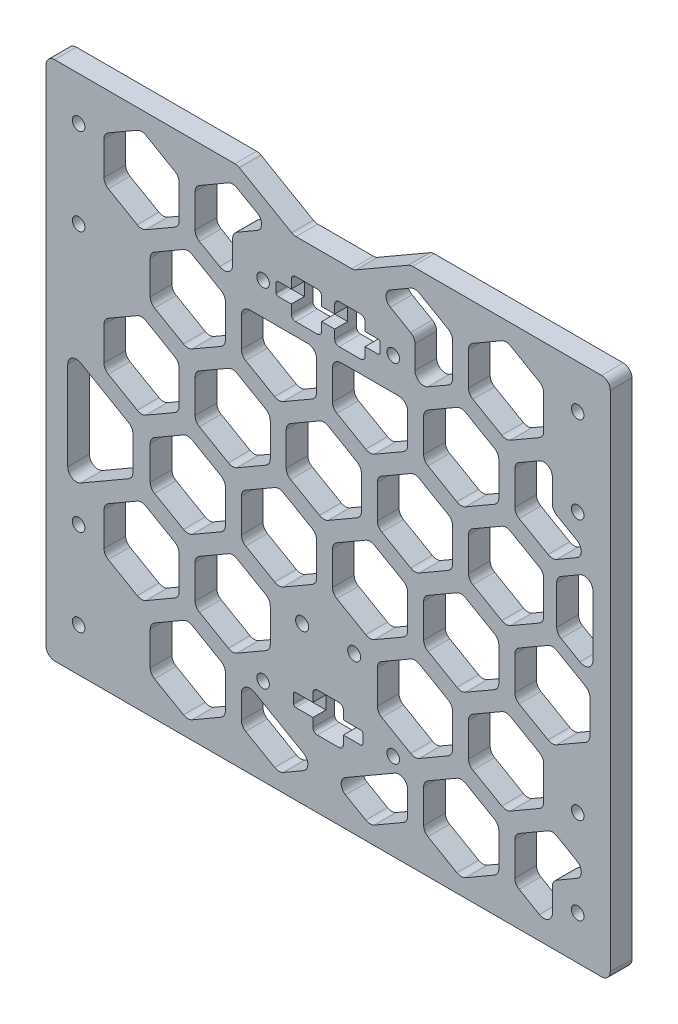
SolidWorks part; units mm, degrees
material "Thornel Mat VMA"
ref_plane "前视基准面" through (0, 0, 0) normal (0, 0, 1) x (1, 0, 0)
ref_plane "上视基准面" through (0, 0, 0) normal (0, 1, 0) x (1, 0, 0)
ref_plane "右视基准面" through (0, 0, 0) normal (1, 0, 0) x (0, 0, -1)
sketch "草图1" plane through (0, 0, 0) normal (0, 0, 1) x (1, 0, 0)
  line L0 (-57.5, -60) -> (-57.5, 60) construction
  line L1 (-65, -60) -> (65, -60)
  line L2 (-65, -60) -> (-65, 60)
  line L3 (-65, 60) -> (65, 60)
  line L4 (65, -60) -> (65, 60)
  line L5 (-65, -60) -> (65, 60) construction
  line L6 (-65, 60) -> (65, -60) construction
  line L7 (0, -1000) -> (0, 49000) construction
  line L8 (57.5, -60) -> (57.5, 60) construction
  line L9 (-57.5, 50) -> (57.5, 30) construction
  line L10 (-57.5, -30) -> (57.5, -50) construction
  line L11 (15, 40) -> (-15, 40) construction
  line L12 (15, -40) -> (-15, -40) construction
  circle A0 centre (-57.5, -50) radius 1.45
  circle A1 centre (-57.5, -30) radius 1.45
  circle A2 centre (-57.5, 30) radius 1.45
  circle A3 centre (-57.5, 50) radius 1.45
  circle A4 centre (57.5, 50) radius 1.45
  circle A5 centre (57.5, 30) radius 1.45
  circle A6 centre (57.5, -30) radius 1.45
  circle A7 centre (57.5, -50) radius 1.45
  circle A8 centre (-15, 40) radius 1.45
  circle A9 centre (15, 40) radius 1.45
  circle A10 centre (-15, -40) radius 1.45
  circle A11 centre (15, -40) radius 1.45
  point P0 (0, 0)
  point P31 (0, 40)
  point P34 (0, -40)
  dimension "D2" = 2.9
  dimension "D9" = 2.9
  dimension "D1" = 130
  dimension "D3" = 20
  dimension "D4" = 60
  dimension "D5" = 20
  dimension "D6" = 10
  dimension "D7" = 10
  dimension "D8" = 7.5
  dimension "D10" = 30
  dimension "D11" = 30
extrude "凸台-拉伸1" add sketch "草图1" along normal blind 5
sketch "草图2" plane through (0, 0, 5) normal (0, 0, 1) x (1, 0, 0)
  line L0 (-57.5, 50) -> (57.5, 30) construction
  line L1 (-8, -41.5) -> (8, -41.5)
  line L2 (-8, -41.5) -> (-8, -38.5)
  line L3 (-8, -38.5) -> (8, -38.5)
  line L4 (8, -41.5) -> (8, -38.5)
  line L5 (-8, -41.5) -> (8, -38.5) construction
  line L6 (-8, -38.5) -> (8, -41.5) construction
  line L7 (-12, 38.5) -> (12, 38.5)
  line L8 (-12, 38.5) -> (-12, 41.5)
  line L9 (-12, 41.5) -> (12, 41.5)
  line L10 (12, 38.5) -> (12, 41.5)
  line L11 (-12, 38.5) -> (12, 41.5) construction
  line L12 (-12, 41.5) -> (12, 38.5) construction
  line L13 (-57.5, -30) -> (57.5, -50) construction
  point P0 (0, -40)
  point P5 (0, 40)
  point P20 (0, 40)
  point P22 (0, -40)
  dimension "D1" = 3
  dimension "D2" = 24
  dimension "D3" = 3
  dimension "D4" = 16
extrude "切除-拉伸1" cut sketch "草图2" against normal blind 3
sketch "草图3" plane through (0, 0, 5) normal (0, 0, 1) x (1, 0, 0)
  line L0 (-57.5, 50) -> (57.5, 30) construction
  line L1 (-57.5, -30) -> (57.5, -50) construction
  line L2 (0, -960) -> (0, 49040) construction
  line L3 (-3.5, -44.5) -> (3.5, -44.5)
  line L4 (-3.5, -44.5) -> (-3.5, -35.5)
  line L5 (-3.5, -35.5) -> (3.5, -35.5)
  line L6 (3.5, -44.5) -> (3.5, -35.5)
  line L7 (-3.5, -44.5) -> (3.5, -35.5) construction
  line L8 (-3.5, -35.5) -> (3.5, -44.5) construction
  line L9 (-8.5, 35.5) -> (-1.5, 35.5)
  line L10 (-8.5, 35.5) -> (-8.5, 44.5)
  line L11 (-8.5, 44.5) -> (-1.5, 44.5)
  line L12 (-1.5, 35.5) -> (-1.5, 44.5)
  line L13 (-8.5, 35.5) -> (-1.5, 44.5) construction
  line L14 (-8.5, 44.5) -> (-1.5, 35.5) construction
  line L15 (8.5, 44.5) -> (1.5, 35.5) construction
  line L16 (8.5, 35.5) -> (1.5, 44.5) construction
  line L17 (1.5, 35.5) -> (1.5, 44.5)
  line L18 (8.5, 44.5) -> (1.5, 44.5)
  line L19 (8.5, 35.5) -> (8.5, 44.5)
  line L20 (8.5, 35.5) -> (1.5, 35.5)
  point P8 (0, -40)
  point P13 (-5, 40)
  point P23 (0, 40)
  point P28 (5, 40)
  dimension "D1" = 5
  dimension "D2" = 7
  dimension "D3" = 9
  dimension "D4" = 7
  dimension "D5" = 9
extrude "切除-拉伸2" cut sketch "草图3" against normal through all
sketch "草图4" plane through (0, 0, 5) normal (0, 0, 1) x (1, 0, 0)
  line L0 (-22, 56) -> (-30.6603, 51)
  line L1 (-43, 56) -> (-51.6603, 51)
  line L2 (-51.6603, 51) -> (-51.6603, 41)
  line L3 (-51.6603, 41) -> (-43, 36)
  line L4 (-43, 36) -> (-34.3397, 41)
  line L5 (-34.3397, 41) -> (-34.3397, 51)
  line L6 (-34.3397, 51) -> (-43, 56)
  line L7 (-32.3397, 37.5359) -> (-41, 32.5359)
  line L8 (-41, 32.5359) -> (-41, 22.5359)
  line L9 (-41, 22.5359) -> (-32.3397, 17.5359)
  line L10 (-32.3397, 17.5359) -> (-23.6795, 22.5359)
  line L11 (-23.6795, 22.5359) -> (-23.6795, 32.5359)
  line L12 (-23.6795, 32.5359) -> (-32.3397, 37.5359)
  line L13 (-30.6603, 51) -> (-30.6603, 41)
  line L14 (-30.6603, 41) -> (-22, 36)
  line L15 (-22, 36) -> (-13.3397, 41) construction
  line L16 (-13.3397, 41) -> (-13.3397, 51) construction
  line L17 (-13.3397, 51) -> (-22, 56)
  line L18 (-11.3397, 37.5359) -> (-20, 32.5359) construction
  line L19 (-20, 32.5359) -> (-20, 22.5359)
  line L20 (-20, 22.5359) -> (-11.3397, 17.5359)
  line L21 (-11.3397, 17.5359) -> (-2.6795, 22.5359)
  line L22 (-2.6795, 22.5359) -> (-2.6795, 32.5359)
  line L23 (-2.6795, 32.5359) -> (-11.3397, 37.5359) construction
  line L24 (-1, 56) -> (-9.6603, 51)
  line L25 (-9.6603, 51) -> (-9.6603, 41)
  line L26 (-9.6603, 41) -> (-1, 36)
  line L27 (-1, 36) -> (7.6603, 41)
  line L28 (7.6603, 41) -> (7.6603, 51)
  line L29 (7.6603, 51) -> (-1, 56)
  line L30 (9.6603, 37.5359) -> (1, 32.5359) construction
  line L31 (1, 32.5359) -> (1, 22.5359)
  line L32 (1, 22.5359) -> (9.6603, 17.5359)
  line L33 (9.6603, 17.5359) -> (18.3205, 22.5359)
  line L34 (18.3205, 22.5359) -> (18.3205, 32.5359)
  line L35 (18.3205, 32.5359) -> (9.6603, 37.5359) construction
  line L36 (20, 56) -> (11.3397, 51)
  line L37 (11.3397, 51) -> (11.3397, 41) construction
  line L38 (11.3397, 41) -> (20, 36) construction
  line L39 (20, 36) -> (28.6603, 41)
  line L40 (28.6603, 41) -> (28.6603, 51)
  line L41 (28.6603, 51) -> (20, 56)
  line L42 (30.6603, 37.5359) -> (22, 32.5359)
  line L43 (22, 32.5359) -> (22, 22.5359)
  line L44 (22, 22.5359) -> (30.6603, 17.5359)
  line L45 (30.6603, 17.5359) -> (39.3205, 22.5359)
  line L46 (39.3205, 22.5359) -> (39.3205, 32.5359)
  line L47 (39.3205, 32.5359) -> (30.6603, 37.5359)
  line L48 (41, 56) -> (32.3397, 51)
  line L49 (32.3397, 51) -> (32.3397, 41)
  line L50 (32.3397, 41) -> (41, 36)
  line L51 (41, 36) -> (49.6603, 41)
  line L52 (49.6603, 41) -> (49.6603, 51)
  line L53 (49.6603, 51) -> (41, 56)
  line L54 (51.6603, 37.5359) -> (43, 32.5359)
  line L55 (43, 32.5359) -> (43, 22.5359)
  line L56 (43, 22.5359) -> (51.6603, 17.5359)
  line L57 (51.6603, 17.5359) -> (60.3205, 22.5359)
  line L58 (60.3205, 22.5359) -> (60.3205, 32.5359) construction
  line L59 (60.3205, 32.5359) -> (51.6603, 37.5359) construction
  line L60 (-22, 19) -> (-30.6603, 14)
  line L61 (-30.6603, 14) -> (-30.6603, 4)
  line L62 (-30.6603, 4) -> (-22, -1)
  line L63 (-22, -1) -> (-13.3397, 4)
  line L64 (-13.3397, 4) -> (-13.3397, 14)
  line L65 (-13.3397, 14) -> (-22, 19)
  line L66 (-11.3397, 0.5359) -> (-20, -4.4641)
  line L67 (-20, -4.4641) -> (-20, -14.4641)
  line L68 (-20, -14.4641) -> (-11.3397, -19.4641)
  line L69 (-11.3397, -19.4641) -> (-2.6795, -14.4641)
  line L70 (-2.6795, -14.4641) -> (-2.6795, -4.4641)
  line L71 (-2.6795, -4.4641) -> (-11.3397, 0.5359)
  line L72 (-1, 19) -> (-9.6603, 14)
  line L73 (-9.6603, 14) -> (-9.6603, 4)
  line L74 (-9.6603, 4) -> (-1, -1)
  line L75 (-1, -1) -> (7.6603, 4)
  line L76 (7.6603, 4) -> (7.6603, 14)
  line L77 (7.6603, 14) -> (-1, 19)
  line L78 (9.6603, 0.5359) -> (1, -4.4641)
  line L79 (1, -4.4641) -> (1, -14.4641)
  line L80 (1, -14.4641) -> (9.6603, -19.4641)
  line L81 (9.6603, -19.4641) -> (18.3205, -14.4641)
  line L82 (18.3205, -14.4641) -> (18.3205, -4.4641)
  line L83 (18.3205, -4.4641) -> (9.6603, 0.5359)
  line L84 (20, 19) -> (11.3397, 14)
  line L85 (11.3397, 14) -> (11.3397, 4)
  line L86 (11.3397, 4) -> (20, -1)
  line L87 (20, -1) -> (28.6603, 4)
  line L88 (28.6603, 4) -> (28.6603, 14)
  line L89 (28.6603, 14) -> (20, 19)
  line L90 (30.6603, 0.5359) -> (22, -4.4641)
  line L91 (22, -4.4641) -> (22, -14.4641)
  line L92 (22, -14.4641) -> (30.6603, -19.4641)
  line L93 (30.6603, -19.4641) -> (39.3205, -14.4641)
  line L94 (39.3205, -14.4641) -> (39.3205, -4.4641)
  line L95 (39.3205, -4.4641) -> (30.6603, 0.5359)
  line L96 (41, 19) -> (32.3397, 14)
  line L97 (32.3397, 14) -> (32.3397, 4)
  line L98 (32.3397, 4) -> (41, -1)
  line L99 (41, -1) -> (49.6603, 4)
  line L100 (49.6603, 4) -> (49.6603, 14)
  line L101 (49.6603, 14) -> (41, 19)
  line L102 (51.6603, 0.5359) -> (43, -4.4641)
  line L103 (43, -4.4641) -> (43, -14.4641)
  line L104 (43, -14.4641) -> (51.6603, -19.4641)
  line L105 (51.6603, -19.4641) -> (60.3205, -14.4641)
  line L106 (60.3205, -14.4641) -> (60.3205, -4.4641)
  line L107 (60.3205, -4.4641) -> (51.6603, 0.5359)
  line L108 (-22, -18) -> (-30.6603, -23)
  line L109 (-30.6603, -23) -> (-30.6603, -33)
  line L110 (-30.6603, -33) -> (-22, -38)
  line L111 (-22, -38) -> (-13.3397, -33)
  line L112 (-13.3397, -33) -> (-13.3397, -23)
  line L113 (-13.3397, -23) -> (-22, -18)
  line L114 (-11.3397, -36.4641) -> (-20, -41.4641) construction
  line L115 (-20, -41.4641) -> (-20, -51.4641)
  line L116 (-20, -51.4641) -> (-11.3397, -56.4641)
  line L117 (-11.3397, -56.4641) -> (-2.6795, -51.4641)
  line L118 (-2.6795, -51.4641) -> (-2.6795, -41.4641) construction
  line L119 (-2.6795, -41.4641) -> (-11.3397, -36.4641) construction
  line L120 (-1, -18) -> (-9.6603, -23)
  line L121 (-9.6603, -23) -> (-9.6603, -33)
  line L122 (-9.6603, -33) -> (-1, -38) construction
  line L123 (-1, -38) -> (7.6603, -33) construction
  line L124 (7.6603, -33) -> (7.6603, -23)
  line L125 (7.6603, -23) -> (-1, -18)
  line L126 (9.6603, -36.4641) -> (1, -41.4641) construction
  line L127 (1, -41.4641) -> (1, -51.4641) construction
  line L128 (1, -51.4641) -> (9.6603, -56.4641)
  line L129 (9.6603, -56.4641) -> (18.3205, -51.4641)
  line L130 (18.3205, -51.4641) -> (18.3205, -41.4641)
  line L131 (18.3205, -41.4641) -> (9.6603, -36.4641) construction
  line L132 (20, -18) -> (11.3397, -23)
  line L133 (11.3397, -23) -> (11.3397, -33)
  line L134 (11.3397, -33) -> (20, -38)
  line L135 (20, -38) -> (28.6603, -33)
  line L136 (28.6603, -33) -> (28.6603, -23)
  line L137 (28.6603, -23) -> (20, -18)
  line L138 (30.6603, -36.4641) -> (22, -41.4641)
  line L139 (22, -41.4641) -> (22, -51.4641)
  line L140 (22, -51.4641) -> (30.6603, -56.4641)
  line L141 (30.6603, -56.4641) -> (39.3205, -51.4641)
  line L142 (39.3205, -51.4641) -> (39.3205, -41.4641)
  line L143 (39.3205, -41.4641) -> (30.6603, -36.4641)
  line L144 (41, -18) -> (32.3397, -23)
  line L145 (32.3397, -23) -> (32.3397, -33)
  line L146 (32.3397, -33) -> (41, -38)
  line L147 (41, -38) -> (49.6603, -33)
  line L148 (49.6603, -33) -> (49.6603, -23)
  line L149 (49.6603, -23) -> (41, -18)
  line L150 (51.6603, -36.4641) -> (43, -41.4641)
  line L151 (43, -41.4641) -> (43, -51.4641)
  line L152 (43, -51.4641) -> (51.6603, -56.4641)
  line L153 (51.6603, -56.4641) -> (60.3205, -51.4641) construction
  line L154 (60.3205, -51.4641) -> (60.3205, -41.4641) construction
  line L155 (60.3205, -41.4641) -> (51.6603, -36.4641)
  line L156 (-43, 19) -> (-51.6603, 14)
  line L157 (-51.6603, 14) -> (-51.6603, 4)
  line L158 (-51.6603, 4) -> (-43, -1)
  line L159 (-43, -1) -> (-34.3397, 4)
  line L160 (-34.3397, 4) -> (-34.3397, 14)
  line L161 (-34.3397, 14) -> (-43, 19)
  line L162 (-32.3397, 0.5359) -> (-41, -4.4641)
  line L163 (-41, -4.4641) -> (-41, -14.4641)
  line L164 (-41, -14.4641) -> (-32.3397, -19.4641)
  line L165 (-32.3397, -19.4641) -> (-23.6795, -14.4641)
  line L166 (-23.6795, -14.4641) -> (-23.6795, -4.4641)
  line L167 (-23.6795, -4.4641) -> (-32.3397, 0.5359)
  line L168 (-43, -18) -> (-51.6603, -23)
  line L169 (-51.6603, -23) -> (-51.6603, -33)
  line L170 (-51.6603, -33) -> (-43, -38)
  line L171 (-43, -38) -> (-34.3397, -33)
  line L172 (-34.3397, -33) -> (-34.3397, -23)
  line L173 (-34.3397, -23) -> (-43, -18)
  line L174 (-32.3397, -36.4641) -> (-41, -41.4641)
  line L175 (-41, -41.4641) -> (-41, -51.4641)
  line L176 (-41, -51.4641) -> (-32.3397, -56.4641)
  line L177 (-32.3397, -56.4641) -> (-23.6795, -51.4641)
  line L178 (-23.6795, -51.4641) -> (-23.6795, -41.4641)
  line L179 (-23.6795, -41.4641) -> (-32.3397, -36.4641)
  line L180 (-9.206, -33.2623) -> (7.6603, -33)
  line L181 (-20, 32.5359) -> (-2.6795, 32.5359)
  line L182 (-13.3397, 51) -> (-22, 46)
  line L183 (-22, 46) -> (-22, 36)
  line L184 (11.3397, 51) -> (20, 46)
  line L185 (20, 46) -> (20, 36)
  line L186 (-20, -41.4641) -> (-2.6795, -51.4641)
  line L187 (1, -51.4641) -> (18.3205, -41.4641)
  line L188 (1, 32.5359) -> (18.3205, 32.5359)
  line L189 (51.6603, 37.5359) -> (51.6603, 27.5359)
  line L190 (51.6603, 27.5359) -> (60.3205, 22.5359)
  line L191 (60.3205, -41.4641) -> (51.6603, -46.4641)
  line L192 (51.6603, -46.4641) -> (51.6603, -56.4641)
  circle A0 centre (-43, 46) radius 8.6603 construction
  circle A1 centre (-32.3397, 27.5359) radius 8.6603 construction
  dimension "D1" = 10
  dimension "D2" = 10
  dimension "D3" = 4
  dimension "D4" = 2
  dimension "D5" = 22
  dimension "D6" = 14
  dimension "D7" = 5
  dimension "D8" = 3
extrude "切除-拉伸3" cut sketch "草图4" against normal through all contours L1 L2 L3 L4 L5 L6 | L7 L8 L9 L10 L11 L12 | L156 L157 L158 L159 L160 L161 | L162 L163 L164 L165 L166 L167 | L168 L169 L170 L171 L172 L173 | L174 L175 L176 L177 L178 L179 | L108 L109 L110 L111 L112 L113 | L66 L67 L68 L69 L70 L71 | L60 L61 L62 L63 L64 L65 | L48 L49 L50 L51 L52 L53 | L42 L43 L44 L45 L46 L47 | L96 L97 L98 L99 L100 L101 | L102 L103 L104 L105 L106 L107 | L90 L91 L92 L93 L94 L95 | L144 L145 L146 L147 L148 L149 | L138 L139 L140 L141 L142 L143 | L132 L133 L134 L135 L136 L137 | L84 L85 L86 L87 L88 L89 | L78 L79 L80 L81 L82 L83 | L72 L73 L74 L75 L76 L77 | L183 L14 L13 L0 L17 L182 | L181 L22 L21 L20 L19 | L185 L39 L40 L41 L36 L184 | L187 L130 L129 L128 | L186 L117 L116 L115 | L188 L34 L33 L32 L31 | L190 L57 L56 L55 L54 L189 | L192 L152 L151 L150 L155 L191
sketch "草图5" plane through (0, 0, 5) normal (0, 0, 1) x (1, 0, 0)
  line L0 (6, -24) -> (-6, -24) construction
  line L1 (-20.9282, 60) -> (-7.9378, 52.5)
  line L2 (65, 60) -> (-65, 60) construction
  line L3 (-7.9378, 52.5) -> (5.9378, 52.5)
  line L4 (5.9378, 52.5) -> (18.9282, 60)
  line L5 (18.9282, 60) -> (-20.9282, 60)
  line L6 (-13.3397, 51) -> (-22, 56) construction
  line L7 (-1.5, 44.5) -> (-8.5, 44.5) construction
  line L8 (20, 56) -> (11.3397, 51) construction
  circle A0 centre (-6, -24) radius 1.5
  circle A1 centre (6, -24) radius 1.5
  point P3 (0, -24)
  dimension "D1" = 3
  dimension "D2" = 12
  dimension "D3" = 24
  dimension "D4" = 4
  dimension "D5" = 8
  dimension "D6" = 4
extrude "切除-拉伸4" cut sketch "草图5" against normal through all
sketch "草图6" plane through (0, 0, 5) normal (0, 0, 1) x (1, 0, 0)
  line L0 (-60, 4.1962) -> (-45, -4.4641)
  line L1 (-45, -4.4641) -> (-45, -14.5359)
  line L2 (-45, -14.5359) -> (-60, -23.1962)
  line L3 (-60, -23.1962) -> (-60, 4.1962)
  line L4 (-51.6603, 4) -> (-43, -1) construction
  line L5 (-41, -4.4641) -> (-41, -14.4641) construction
  line L6 (-43, -18) -> (-51.6603, -23) construction
  line L7 (-65, 60) -> (-65, -60) construction
  line L8 (61, 19.4641) -> (52.6603, 14.6491)
  line L9 (52.6603, 14.6491) -> (52.6603, 3.4226)
  line L10 (52.6603, 3.4226) -> (61, -1.3923)
  line L11 (61, -1.3923) -> (61, 19.4641)
  line L12 (65, -60) -> (65, 60) construction
  line L13 (51.6603, 17.5359) -> (60.3205, 22.5359) construction
  line L14 (49.6603, 4) -> (49.6603, 14) construction
  line L16 (60.3205, -4.4641) -> (51.6603, 0.5359) construction
  dimension "D1" = 4
  dimension "D2" = 4
  dimension "D3" = 4
  dimension "D4" = 5
  dimension "D5" = 4
  dimension "D6" = 3
  dimension "D7" = 3
  dimension "D8" = 3
extrude "切除-拉伸5" cut sketch "草图6" against normal through all
fillet "圆角1" radius 2 170 edges at (51.6603, -56.4641, 2.5) (43, -51.4641, 2.5) (43, -41.4641, 2.5) (51.6603, -36.4641, 2.5) (60.3205, -41.4641, 2.5) (51.6603, -46.4641, 2.5) (60.3205, 22.5359, 2.5) (51.6603, 17.5359, 2.5) (43, 22.5359, 2.5) (43, 32.5359, 2.5) (51.6603, 37.5359, 2.5) (51.6603, 27.5359, 2.5) (-22, 36, 2.5) (-30.6603, 41, 2.5) (-30.6603, 51, 2.5) (-22, 56, 2.5) (-13.3397, 51, 2.5) (-22, 46, 2.5) (-34.3397, 51, 2.5) (-34.3397, 41, 2.5) (-43, 36, 2.5) (-51.6603, 41, 2.5) (-51.6603, 51, 2.5) (-43, 56, 2.5) (-20, -41.4641, 2.5) (-2.6795, -51.4641, 2.5) (-11.3397, -56.4641, 2.5) (-20, -51.4641, 2.5) (1, -51.4641, 2.5) (18.3205, -41.4641, 2.5) (18.3205, -51.4641, 2.5) (9.6603, -56.4641, 2.5) (11.3397, 51, 2.5) (20, 56, 2.5) (28.6603, 51, 2.5) (28.6603, 41, 2.5) (20, 36, 2.5) (20, 46, 2.5) (-20, 32.5359, 2.5) (-2.6795, 32.5359, 2.5) (-2.6795, 22.5359, 2.5) (-11.3397, 17.5359, 2.5) (-20, 22.5359, 2.5) (18.3205, -4.4641, 2.5) (18.3205, -14.4641, 2.5) (9.6603, -19.4641, 2.5) (1, -14.4641, 2.5) (1, -4.4641, 2.5) (9.6603, 0.5359, 2.5) (28.6603, 14, 2.5) (28.6603, 4, 2.5) (20, -1, 2.5) (11.3397, 4, 2.5) (11.3397, 14, 2.5) (20, 19, 2.5) (7.6603, 14, 2.5) (7.6603, 4, 2.5) (-1, -1, 2.5) (-9.6603, 4, 2.5) (-9.6603, 14, 2.5) (-1, 19, 2.5) (1, 32.5359, 2.5) (18.3205, 32.5359, 2.5) (18.3205, 22.5359, 2.5) (9.6603, 17.5359, 2.5) (1, 22.5359, 2.5) (49.6603, 14, 2.5) (49.6603, 4, 2.5) (41, -1, 2.5) (32.3397, 4, 2.5) (32.3397, 14, 2.5) (41, 19, 2.5) (60.3205, -4.4641, 2.5) (60.3205, -14.4641, 2.5) (51.6603, -19.4641, 2.5) (43, -14.4641, 2.5) (43, -4.4641, 2.5) (51.6603, 0.5359, 2.5) (49.6603, 51, 2.5) (49.6603, 41, 2.5) (41, 36, 2.5) (32.3397, 41, 2.5) (32.3397, 51, 2.5) (41, 56, 2.5) (39.3205, 32.5359, 2.5) (39.3205, 22.5359, 2.5) (30.6603, 17.5359, 2.5) (22, 22.5359, 2.5) (22, 32.5359, 2.5) (30.6603, 37.5359, 2.5) (39.3205, -41.4641, 2.5) (39.3205, -51.4641, 2.5) (30.6603, -56.4641, 2.5) (22, -51.4641, 2.5) (22, -41.4641, 2.5) (30.6603, -36.4641, 2.5) (28.6603, -23, 2.5) (28.6603, -33, 2.5) (20, -38, 2.5) (11.3397, -33, 2.5) (11.3397, -23, 2.5) (20, -18, 2.5) (39.3205, -4.4641, 2.5) (39.3205, -14.4641, 2.5) (30.6603, -19.4641, 2.5) (22, -14.4641, 2.5) (22, -4.4641, 2.5) (30.6603, 0.5359, 2.5) (49.6603, -23, 2.5) (49.6603, -33, 2.5) (41, -38, 2.5) (32.3397, -33, 2.5) (32.3397, -23, 2.5) (41, -18, 2.5) (-23.6795, -4.4641, 2.5) (-23.6795, -14.4641, 2.5) (-32.3397, -19.4641, 2.5) (-41, -14.4641, 2.5) (-41, -4.4641, 2.5) (-32.3397, 0.5359, 2.5) (-34.3397, -23, 2.5) (-34.3397, -33, 2.5) (-43, -38, 2.5) (-51.6603, -33, 2.5) (-51.6603, -23, 2.5) (-43, -18, 2.5) (-23.6795, 32.5359, 2.5) (-23.6795, 22.5359, 2.5) (-32.3397, 17.5359, 2.5) (-41, 22.5359, 2.5) (-41, 32.5359, 2.5) (-32.3397, 37.5359, 2.5) (-34.3397, 14, 2.5) (-34.3397, 4, 2.5) (-43, -1, 2.5) (-51.6603, 4, 2.5) (-51.6603, 14, 2.5) (-43, 19, 2.5) (-2.6795, -4.4641, 2.5) (-2.6795, -14.4641, 2.5) (-11.3397, -19.4641, 2.5) (-20, -14.4641, 2.5) (-20, -4.4641, 2.5) (-11.3397, 0.5359, 2.5) (-13.3397, 14, 2.5) (-13.3397, 4, 2.5) (-22, -1, 2.5) (-30.6603, 4, 2.5) (-30.6603, 14, 2.5) (-22, 19, 2.5) (-23.6795, -41.4641, 2.5) (-23.6795, -51.4641, 2.5) (-32.3397, -56.4641, 2.5) (-41, -51.4641, 2.5) (-41, -41.4641, 2.5) (-32.3397, -36.4641, 2.5) (-13.3397, -23, 2.5) (-13.3397, -33, 2.5) (-22, -38, 2.5) (-30.6603, -33, 2.5) (-30.6603, -23, 2.5) (-22, -18, 2.5) (61, -1.3923, 2.5) (52.6603, 3.4226, 2.5) (52.6603, 14.6491, 2.5) (61, 19.4641, 2.5) (-60, 4.1962, 2.5) (-45, -14.5359, 2.5) (-60, -23.1962, 2.5) (-45, -4.4641, 2.5)
fillet "圆角2" radius 1 12 edges at (3.5, -44.5, 2.5) (-3.5, -44.5, 2.5) (3.5, -35.5, 2.5) (-3.5, -35.5, 2.5) (8.5, 35.5, 2.5) (1.5, 35.5, 2.5) (8.5, 44.5, 2.5) (1.5, 44.5, 2.5) (-1.5, 35.5, 2.5) (-8.5, 35.5, 2.5) (-1.5, 44.5, 2.5) (-8.5, 44.5, 2.5)
fillet "圆角3" radius 0.5 8 edges at (12, 38.5, 3.5) (12, 41.5, 3.5) (-12, 38.5, 3.5) (-12, 41.5, 3.5) (8, -41.5, 3.5) (8, -38.5, 3.5) (-8, -41.5, 3.5) (-8, -38.5, 3.5)
fillet "圆角4" radius 2 8 edges at (65, 60, 2.5) (65, -60, 2.5) (-65, -60, 2.5) (-20.9282, 60, 2.5) (-7.9378, 52.5, 2.5) (5.9378, 52.5, 2.5) (18.9282, 60, 2.5) (-65, 60, 2.5)
